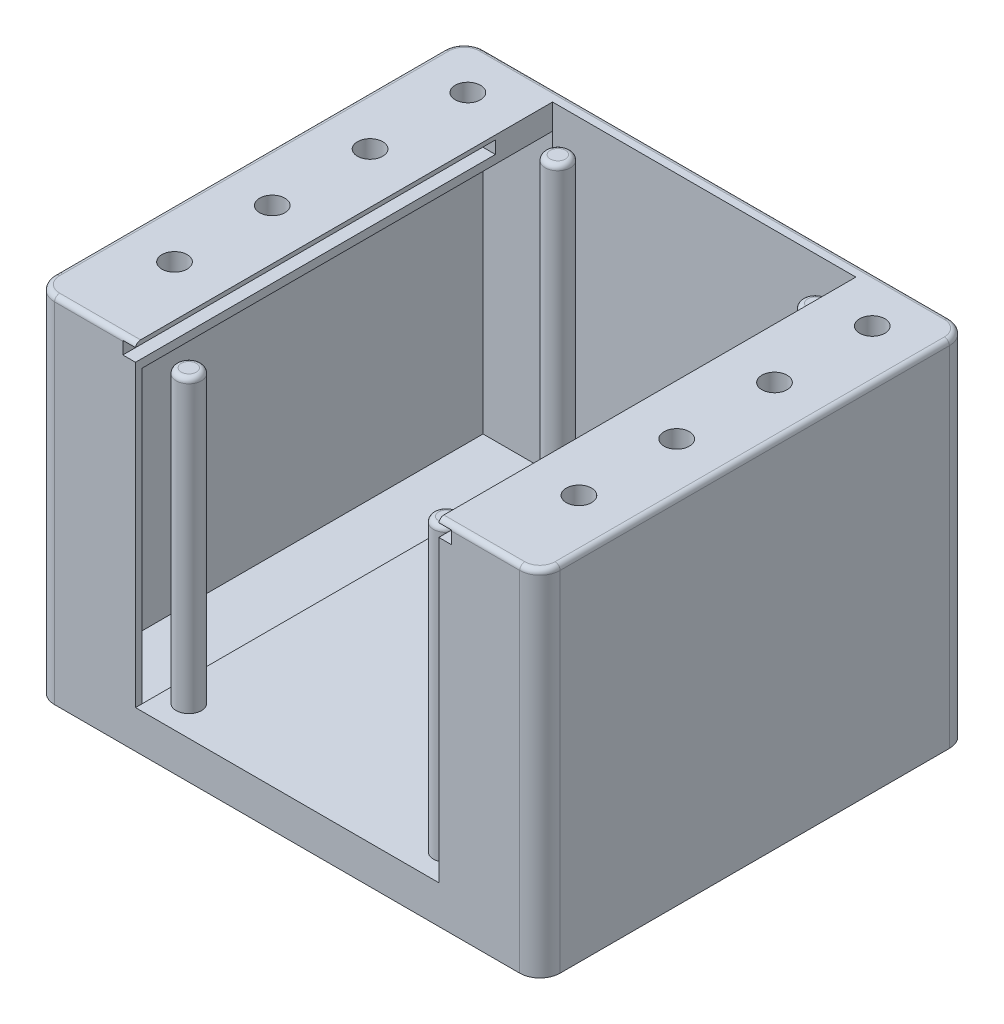
SolidWorks part; units mm, degrees
material "ABS"
ref_plane "Front Plane" through (0, 0, 0) normal (0, 0, 1) x (1, 0, 0)
ref_plane "Top Plane" through (0, 0, 0) normal (0, 1, 0) x (1, 0, 0)
ref_plane "Right Plane" through (0, 0, 0) normal (1, 0, 0) x (0, 0, -1)
sketch "Sketch1" plane through (0, 0, 0) normal (0, 1, 0) x (1, 0, 0)
  line L1 (254, -215.9) -> (-254, -215.9)
  line L2 (254, -215.9) -> (254, 215.9)
  line L3 (254, 215.9) -> (-254, 215.9)
  line L4 (-254, -215.9) -> (-254, 215.9)
  line L5 (254, -215.9) -> (-254, 215.9) construction
  line L6 (254, 215.9) -> (-254, -215.9) construction
  point P0 (0, 0)
  dimension "D1" = 508
  dimension "D2" = 431.8
extrude "Boss-Extrude1" add sketch "Sketch1" along normal blind 355.6
sketch "Sketch2" plane through (0, 355.6, 0) normal (0, 1, 0) x (1, 0, 0)
  line L0 (-152.4, -215.9) -> (-152.4, 203.2)
  line L3 (-254, -215.9) -> (254, -215.9) construction
  line L4 (-152.4, 203.2) -> (152.4, 203.2)
  line L5 (152.4, 203.2) -> (152.4, -215.9)
  line L6 (152.4, -215.9) -> (-152.4, -215.9)
  point P0 (0, 0)
  point P9 (0, 203.2)
  dimension "D1" = 304.8
  dimension "D2" = 419.1
extrude "Cut-Extrude1" cut sketch "Sketch2" against normal blind 317.5
sketch "Sketch3" plane through (152.4, 0, 0) normal (-1, 0, 0) x (0, 0, 1)
  line L1 (-209.55, 330.2) -> (209.55, 330.2)
  line L2 (-209.55, 330.2) -> (-209.55, 25.4)
  line L3 (-209.55, 25.4) -> (209.55, 25.4)
  line L4 (209.55, 330.2) -> (209.55, 25.4)
  point P5 (0, 330.2)
  dimension "D1" = 419.1
  dimension "D2" = 304.8
  dimension "D3" = 330.2
extrude "Cut-Extrude2" cut sketch "Sketch3" against normal blind 76.2
sketch "Sketch4" plane through (0, 355.6, 0) normal (0, 1, 0) x (1, 0, 0)
  line L0 (152.4, -215.9) -> (254, -215.9) construction
  circle A0 centre (203.2, 168.879) radius 12.7
  point P6 (203.2, -215.9)
  dimension "D1" = 25.4
  dimension "D2" = 168.879
extrude "Cut-Extrude3" cut sketch "Sketch4" against normal up to next
sketch "Sketch5" plane through (0, 355.6, 0) normal (0, 1, 0) x (1, 0, 0)
  line L0 (203.2, 168.879) -> (203.2, -215.9) construction
  line L1 (152.4, -215.9) -> (254, -215.9) construction
pattern_linear "LPattern1" count 4 spacing 98.26 along (0, 0, 1) of "Cut-Extrude3"
mirror "Mirror2" about plane through (0, 0, 0) normal (1, 0, 0) of "LPattern1", "Cut-Extrude3", "Cut-Extrude2"
sketch "Sketch6" plane through (0, 0, 215.9) normal (0, 0, 1) x (1, 0, 0)
  line L0 (152.4, 338.6401) -> (165.1, 338.6401)
  line L1 (152.4, 38.1) -> (152.4, 355.6) construction
  line L2 (165.1, 338.6401) -> (165.1, 351.3401)
  line L3 (165.1, 351.3401) -> (152.4, 351.3401)
  line L4 (-254, 0) -> (254, 0) construction
  point P8 (0, 0)
  dimension "D1" = 12.7
  dimension "D2" = 12.7
  dimension "D3" = 338.6401
extrude "Cut-Extrude4" cut sketch "Sketch6" against normal blind 361.696 and the other way through all
mirror "Mirror3" about plane through (0, 0, 0) normal (1, 0, 0) of "Cut-Extrude4"
sketch "Sketch8" plane through (0, 38.1, 0) normal (0, 1, 0) x (1, 0, 0)
  circle A0 centre (-129.286, 185.42) radius 12.7
  circle A1 centre (-129.286, -185.42) radius 12.7
  dimension "D1" = 25.4
  dimension "D2" = 25.4
  dimension "D3" = 129.286
  dimension "D4" = 185.42
  dimension "D5" = 185.42
extrude "Boss-Extrude2" add sketch "Sketch8" along normal blind 292.1
mirror "Mirror4" about plane through (0, 0, 0) normal (1, 0, 0) of "Boss-Extrude2"
fillet "Fillet1" radius 5.08 9 edges at (129.286, 330.2, -172.72) (-129.286, 330.2, -172.72) (129.286, 330.2, 198.12) (-129.286, 330.2, 198.12) (203.2, 355.6, 215.9) (254, 355.6, 0) (0, 355.6, -215.9) (-203.2, 355.6, 215.9) (-254, 355.6, 0)
fillet "Fillet2" radius 20.32 8 edges at (-252.5121, 354.1121, 214.4121) (-252.5121, 354.1121, -214.4121) (252.5121, 354.1121, -214.4121) (252.5121, 354.1121, 214.4121) (254, 175.26, 215.9) (254, 175.26, -215.9) (-254, 175.26, -215.9) (-254, 175.26, 215.9)
